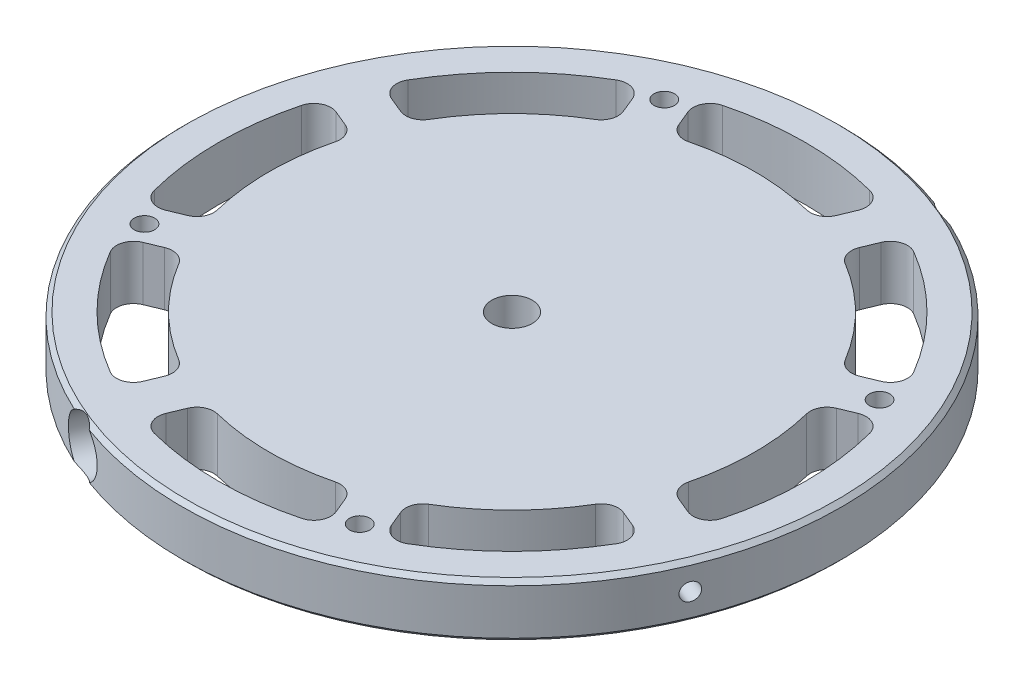
SolidWorks part; units mm, degrees
material "6061-T6 (SS)"
ref_plane "Front Plane" through (0, 0, 0) normal (0, 0, 1) x (1, 0, 0)
ref_plane "Top Plane" through (0, 0, 0) normal (0, 1, 0) x (1, 0, 0)
ref_plane "Right Plane" through (0, 0, 0) normal (1, 0, 0) x (0, 0, -1)
sketch "Sketch2" plane through (0, 0, 0) normal (1, 0, 0) x (0, 0, -1)
  line L0 (0, 0) -> (-77.55, 0)
  line L1 (-77.55, 0) -> (-77.55, 12.7)
  line L2 (-77.55, 12.7) -> (0, 12.7)
  line L5 (0, 12.7) -> (0, 0)
  dimension "D1" = 77.55
  dimension "D2" = 12.7
ref_axis "Axis1" through (0, -0.8888, 0) along (0, 1, 0)
revolve "Revolve1" add sketch "Sketch2" angle 360 about axis through (0, -0.8888, 0) along (0, 1, 0)
hole_wizard "#12 (0.189) Diameter Hole1" positions "Sketch6" profile "Sketch7" hole size "#12" standard "ANSI Inch" end condition through all
sketch "Sketch6" plane through (0, 12.7, 0) normal (0, 1, 0) x (1, 0, 0)
  line L0 (0, 0) -> (-53.438, 129.0108) construction
  line L2 (0, 0) -> (0, 109.0908) construction
  point P0 (-25.3336, 61.1608)
  dimension "D1" = 22.5
  dimension "D2" = 66.2
sketch "Sketch7" plane through (-25.3336, 12.7, -61.1608) normal (1, 0, 0) x (0, 0, 1)
  line L0 (0, 0) -> (0, 12.7)
  line L1 (0, 12.7) -> (2.4003, 12.7)
  line L2 (2.4003, 12.7) -> (2.4003, 0)
  line L5 (2.4003, 0) -> (0, 0)
  line L11 (0, -6.35) -> (0, 107.95) construction
  dimension "Thru Hole Dia." = 4.8006
  dimension "Thru Hole Depth" = 12.7
pattern_circular "CirPattern3" count 4 over 360 about axis through (0, -0.8888, 0) along (0, 1, 0) of "#12 (0.189) Diameter Hole1"
sketch "Sketch8" plane through (0, 12.7, 0) normal (0, 1, 0) x (1, 0, 0)
  line L4 (0, 0) -> (0, 93.9995) construction
  line L5 (0, 0) -> (113.8372, 0) construction
  line L6 (-17.1671, 54.5107) -> (-21.7355, 65.5398)
  line L7 (17.1671, 54.5107) -> (21.7355, 65.5398)
  line L8 (0, 0) -> (-25.3336, 61.1608) construction
  arc A0 (-17.1671, 54.5107) -> (17.1671, 54.5107) centre (0, 0) cw
  arc A1 (-21.7355, 65.5398) -> (21.7355, 65.5398) centre (0, 0) cw
  circle A2 centre (0, 0) radius 77.55 construction
  dimension "D1" = 57.15
  dimension "D2" = 8.5
  dimension "D3" = 5
extrude "Cut-Extrude1" cut sketch "Sketch8" against normal through all
fillet "Fillet1" radius 4 4 edges at (17.1671, 6.35, -54.5107) (21.7355, 6.35, -65.5398) (-17.1671, 6.35, -54.5107) (-21.7355, 6.35, -65.5398)
pattern_circular "CirPattern4" count 8 over 360 about axis through (0, -0.8888, 0) along (0, 1, 0) of "Cut-Extrude1", "Fillet1"
chamfer "Chamfer1" distance 1 angle 45 2 edges at (0, 0, -77.55) (0, 12.7, -77.55)
ref_plane "Plane1" through (0, 0, 0) normal (0.9239, 0, 0.3827) x (0, 1, 0)
hole_wizard "#20 (0.161) Diameter Hole1" positions "Sketch16" profile "Sketch15" hole size "#20" standard "ANSI Inch" end condition through all
sketch "Sketch16" plane through (0, 0, 0) normal (0.9239, 0, 0.3827) x (0, 1, 0)
  point P0 (6.35, 0)
  dimension "D1" = 6.35
sketch "Sketch15" plane through (0, 6.35, 0) normal (0, 1, 0) x (-0.3827, 0, 0.9239)
  line L0 (0, 0) -> (0, 101.324)
  line L1 (0, 101.324) -> (2.0447, 101.324)
  line L2 (2.0447, 101.324) -> (2.0447, 0)
  line L5 (2.0447, 0) -> (0, 0)
  line L11 (0, -6.35) -> (0, 107.95) construction
  dimension "Thru Hole Dia." = 4.0894
  dimension "Thru Hole Depth" = 101.324
ref_plane "Plane2" through (29.6771, 0, -71.6469) normal (0.3827, 0, -0.9239) x (-0.9239, 0, -0.3827)
sketch "Sketch19" plane through (29.6771, 0, -71.6469) normal (0.3827, 0, -0.9239) x (-0.9239, 0, -0.3827)
  line L0 (-76.55, 0) -> (76.55, 0) construction
  line L2 (0, -0.8888) -> (0, 13.5888) construction
  circle A0 centre (0, 6.35) radius 5.5625 construction
  circle A1 centre (0, 6.35) radius 6.25
  dimension "D1" = 12.5
  dimension "D2" = 6.35
extrude "Cut-Extrude3" cut sketch "Sketch19" against normal blind 5
pattern_circular "CirPattern5" count 2 over 360 about axis through (0, -0.8888, 0) along (0, 1, 0) of "Cut-Extrude3"
hole_wizard "#10-24 Tapped Hole1" positions "Sketch20" profile "Sketch21" tap size "#10-24" standard "ANSI Inch"
sketch "Sketch20" plane through (-27.7637, 0, 67.0275) normal (-0.3827, 0, 0.9239) x (0.9239, 0, 0.3827)
  circle A0 centre (0, 6.35) radius 6.25
  circle A1 centre (0, 6.35) radius 6.25 construction
  point P0 (0, 6.35)
sketch "Sketch21" plane through (-27.7637, 6.35, 67.0275) normal (0, 1, 0) x (0.9239, 0, 0.3827)
  line L0 (0, 0) -> (0, 51.9408)
  line L1 (0, 51.9408) -> (1.8986, 50.8)
  line L2 (1.8986, 50.8) -> (1.8986, 0)
  line L5 (1.8986, 0) -> (0, 0)
  line L10 (0, 51.9408) -> (-1.8986, 50.8) construction
  line L11 (0, -6.35) -> (0, 107.95) construction
  dimension "Tap Drill Dia." = 3.7973
  dimension "Tap Drill Depth" = 50.8
  dimension "Drill Angle" = 118
pattern_circular "CirPattern6" count 2 over 360 about axis through (0, -0.8888, 0) along (0, 1, 0) of "#10-24 Tapped Hole1"
sketch "Sketch22" plane through (0, 12.7, 0) normal (0, 1, 0) x (1, 0, 0)
  circle A0 centre (0, 0) radius 4.765
  dimension "D1" = 9.53
extrude "Cut-Extrude4" cut sketch "Sketch22" against normal blind 12.8
equation "\"TubeDiameter\" = 6.500in"
equation "\"D1@Sketch2\"=(\"TubeDiameter\"/2)-5mm"
equation "\"D2@Sketch6\"=66.2"
